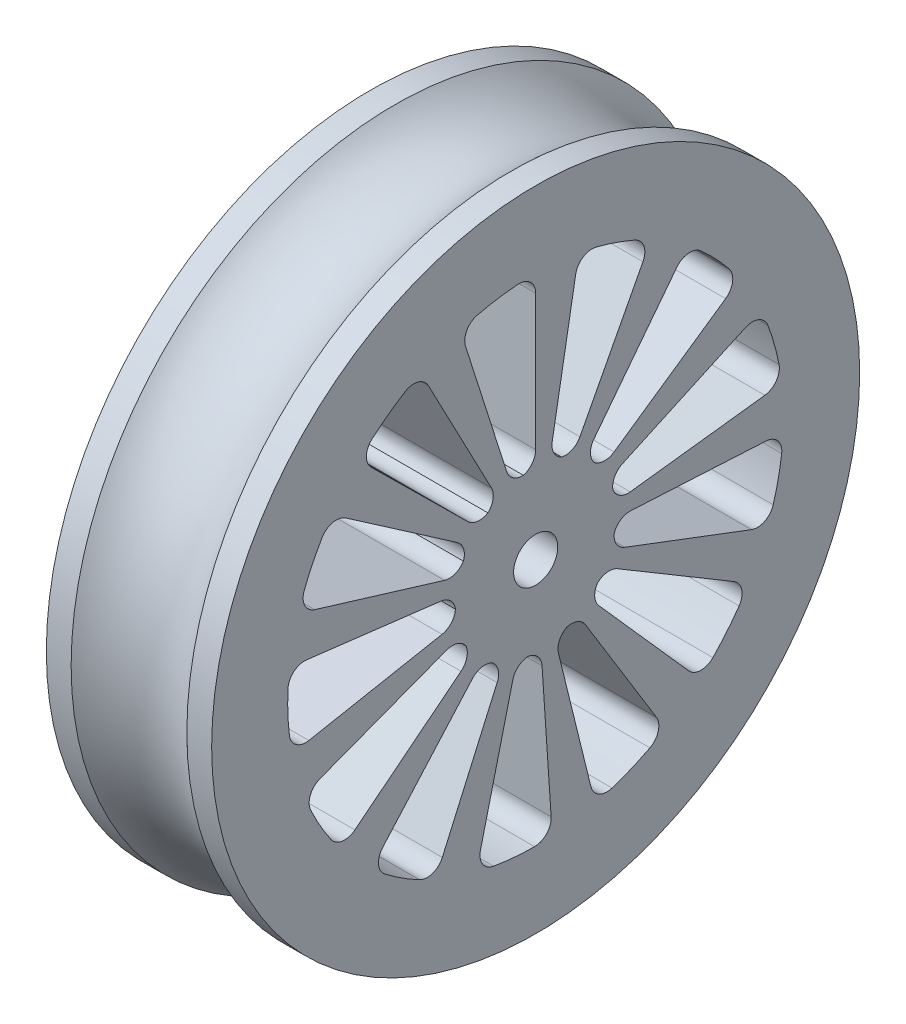
SolidWorks part; units mm, degrees
ref_plane "Front Plane" through (0, 0, 0) normal (0, 0, 1) x (1, 0, 0)
ref_plane "Top Plane" through (0, 0, 0) normal (0, 1, 0) x (1, 0, 0)
ref_plane "Right Plane" through (0, 0, 0) normal (1, 0, 0) x (0, 0, -1)
sketch "Sketch1" plane through (0, 0, 0) normal (0, 0, 1) x (1, 0, 0)
  line L0 (0, 0) -> (10, 0)
  line L1 (0, 0) -> (0, 19.6)
  line L2 (10, 19.6) -> (10, 0)
  line L3 (0, 0) -> (34.8651, 0) construction
  line L4 (0, 19.6) -> (1.5, 19.6)
  line L5 (10, 19.6) -> (8.5, 19.6)
  arc A1 (1.5, 19.6) -> (8.5, 19.6) centre (5, 23.1707) ccw
  dimension "D3" = 1.5
  dimension "D4" = 1.5
  dimension "D5" = 5
  dimension "D1" = 10
  dimension "D2" = 19.6
revolve "Revolve2" add sketch "Sketch1" angle 360 about L3
sketch "Sketch2" plane through (10, 0, 0) normal (1, 0, 0) x (0, 0, -1)
  circle A0 centre (0, 0) radius 1.335
  dimension "D1" = 2.67
sketch "Sketch3" plane through (10, 0, 0) normal (1, 0, 0) x (0, 0, -1)
  line L0 (0, 0) -> (0, 23.0393) construction
  line L1 (0, 4.8503) -> (0, 15)
  line L2 (0.8423, 4.7766) -> (2.6047, 14.7721)
  line L3 (2.9656, 3.8381) -> (9.1713, 11.8696)
  line L4 (2.2541, 4.2948) -> (6.9708, 13.2818)
  line L5 (4.4096, 2.0203) -> (13.6369, 6.2479)
  line L6 (3.9917, 2.7553) -> (12.3448, 8.521)
  line L7 (4.8433, -0.2603) -> (14.9784, -0.8051)
  line L8 (4.815, 0.5846) -> (14.8906, 1.8081)
  line L9 (4.1676, -2.4813) -> (12.8885, -7.6737)
  line L10 (4.5351, -1.7199) -> (14.0252, -5.3191)
  line L11 (2.5371, -4.1339) -> (7.8461, -12.7843)
  line L12 (3.2164, -3.6305) -> (9.9468, -11.2277)
  line L13 (0.3253, -4.8394) -> (1.0062, -14.9662)
  line L14 (1.1608, -4.7094) -> (3.5897, -14.5641)
  line L15 (-1.9609, -4.4363) -> (-6.0642, -13.7195)
  line L16 (-1.1608, -4.7094) -> (-3.5897, -14.5641)
  line L17 (-3.7979, -3.0169) -> (-11.7454, -9.3298)
  line L18 (-3.2164, -3.6305) -> (-9.9468, -11.2277)
  line L19 (-4.7649, -0.9063) -> (-14.7358, -2.8028)
  line L20 (-4.5351, -1.7199) -> (-14.0252, -5.3191)
  line L21 (-4.6403, 1.4119) -> (-14.3504, 4.3663)
  line L22 (-4.815, 0.5846) -> (-14.8906, 1.8081)
  line L23 (-3.4526, 3.4066) -> (-10.6776, 10.5352)
  line L24 (-3.9917, 2.7553) -> (-12.3448, 8.521)
  line L25 (-1.474, 4.6209) -> (-4.5586, 14.2905)
  line L26 (-2.2541, 4.2948) -> (-6.9708, 13.2818)
  circle A0 centre (0, 0) radius 15
  circle A1 centre (0, 0) radius 4.8503
  point P59 (0, 0)
  dimension "D1" = 15
  dimension "D2" = 10
  dimension "D3" = 13
extrude "Cut-Extrude2" cut sketch "Sketch3" against normal through all contours A1 L4 A0 L2 | A1 L6 A0 L3 | A1 L8 A0 L5 | A1 L10 A0 L7 | A1 L12 A0 L9 | A1 L14 A0 L11 | A1 L16 A0 L13 | A1 L18 A0 L15 | A1 L20 A0 L17 | A1 L22 A0 L19 | A1 L24 A0 L21 | A1 L26 A0 L23 | A1 L1 A0 L25 region at (10, 10.6194, 1.6527) region at (10, 10.1711, -3.4717) region at (10, 8.635, 6.3985) region at (10, 7.3927, -7.8008) region at (10, 4.6724, 9.6785) region at (10, 2.9207, -10.3428) region at (10, -0.3607, 10.7412) region at (10, -2.2204, -10.5154) region at (10, -5.311, 9.3433) region at (10, -6.8528, -8.2791) region at (10, -9.0447, 5.8049) region at (10, -9.9153, -4.1461) region at (10, -10.7064, 0.9367)
fillet "Fillet1" radius 1 52 edges at (5, 14.2905, 4.5586) (5, 14.7721, -2.6047) (5, 10.5352, 10.6776) (5, 4.3663, 14.3504) (5, 1.8081, 14.8906) (5, -5.3191, 14.0252) (5, -11.2277, 9.9468) (5, -14.5641, 3.5897) (5, -14.5641, -3.5897) (5, 11.8696, -9.1713) (5, -5.3191, -14.0252) (5, -0.8051, -14.9784) (5, 1.8081, -14.8906) (5, 6.2479, -13.6369) (5, 8.521, -12.3448) (5, 13.2818, -6.9708) (5, 15, 0) (5, 13.2818, 6.9708) (5, 8.521, 12.3448) (5, -2.8028, 14.7358) (5, -9.3298, 11.7454) (5, -13.7195, 6.0642) (5, -14.9662, -1.0062) (5, -12.7843, -7.8461) (5, -11.2277, -9.9468) (5, -7.6737, -12.8885) (5, 4.6209, 1.474) (5, 4.8503, 0) (5, 3.4066, 3.4526) (5, 4.2948, 2.2541) (5, 1.4119, 4.6403) (5, 2.7553, 3.9917) (5, -0.9063, 4.7649) (5, 0.5846, 4.815) (5, -3.0169, 3.7979) (5, -1.7199, 4.5351) (5, -3.6305, 3.2164) (5, -4.4363, 1.9609) (5, -4.7094, 1.1608) (5, -4.8394, -0.3253) (5, -4.7094, -1.1608) (5, -4.1339, -2.5371) (5, -3.6305, -3.2164) (5, -2.4813, -4.1676) (5, -1.7199, -4.5351) (5, -0.2603, -4.8433) (5, 0.5846, -4.815) (5, 2.0203, -4.4096) (5, 2.7553, -3.9917) (5, 4.7766, -0.8423) (5, 4.2948, -2.2541) (5, 3.8381, -2.9656)
sketch "Sketch4" plane through (10, 0, 0) normal (1, 0, 0) x (0, 0, -1)
extrude "Cut-Extrude3" cut sketch "Sketch2" against normal blind 3.45
sketch "Sketch5" plane through (6.55, 0, 0) normal (1, 0, 0) x (0, 0, -1)
  line L0 (-0.948, 0.94) -> (0.948, 0.94)
  arc A0 (-0.948, 0.94) -> (0.948, 0.94) centre (0, 0) ccw
  dimension "D2" = 2.67
  dimension "D1" = 0.94
extrude "Cut-Extrude5" cut sketch "Sketch5" against normal through all
